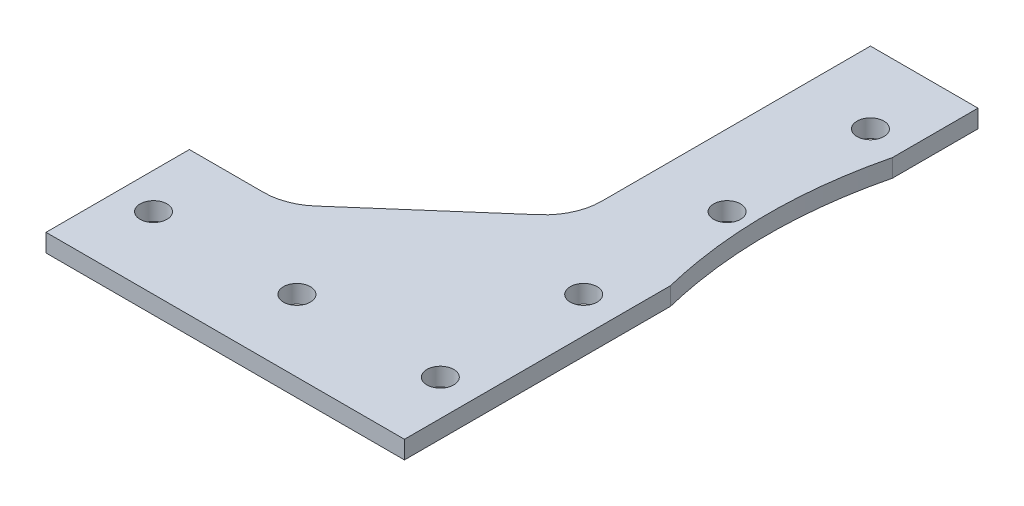
SolidWorks part; units mm, degrees
ref_plane "Front Plane" through (0, 0, 0) normal (0, 0, 1) x (1, 0, 0)
ref_plane "Top Plane" through (0, 0, 0) normal (0, 1, 0) x (1, 0, 0)
ref_plane "Right Plane" through (0, 0, 0) normal (1, 0, 0) x (0, 0, -1)
sketch "Sketch1" plane through (0, 0, 0) normal (0, 1, 0) x (1, 0, 0)
  line L1 (-31.75, 50.8) -> (31.75, 50.8)
  line L2 (-31.75, 50.8) -> (-31.75, -50.8)
  line L3 (-31.75, -50.8) -> (31.75, -50.8)
  line L4 (31.75, 50.8) -> (31.75, -50.8)
  line L5 (-31.75, 50.8) -> (31.75, -50.8) construction
  line L6 (-31.75, -50.8) -> (31.75, 50.8) construction
  point P0 (0, 0)
  dimension "D1" = 101.6
  dimension "D2" = 63.5
extrude "Boss-Extrude1" add sketch "Sketch1" along normal blind 3.175
sketch "Sketch2" plane through (0, 3.175, 0) normal (0, 1, 0) x (1, 0, 0)
  line L0 (-31.75, -50.8) -> (31.75, -50.8) construction
  line L1 (31.75, -50.8) -> (31.75, 50.8) construction
  circle A0 centre (25.4, -38.1) radius 2.3812
  circle A1 centre (25.4, -12.7) radius 2.3812
  circle A2 centre (25.4, 12.7) radius 2.3812
  circle A3 centre (25.4, 38.1) radius 2.3812
  circle A4 centre (0, -38.1) radius 2.3812
  circle A5 centre (-25.4, -38.1) radius 2.3812
  circle A6 centre (-50.8, -38.1) radius 2.3812
  dimension "D1" = 4.7625
  dimension "D2" = 12.7
  dimension "D3" = 6.35
  dimension "D4" = 4
  dimension "D5" = 4
extrude "Cut-Extrude1" cut sketch "Sketch2" against normal blind 3.175
sketch "Sketch3" plane through (0, 3.175, 0) normal (0, 1, 0) x (1, 0, 0)
  line L1 (-31.75, 50.8) -> (-31.75, -50.8) construction
  line L2 (31.75, 50.8) -> (-31.75, 50.8) construction
  line L3 (25.6187, 50.8) -> (-31.75, 50.8)
  line L4 (-31.75, 50.8) -> (-31.75, -36.9013)
  line L5 (-31.75, -25.4) -> (-14.7816, -25.4)
  line L6 (-14.7816, -25.4) -> (12.7, -1.3949)
  line L7 (12.7, -1.3949) -> (12.7, 50.8)
  line L8 (12.7, 50.8) -> (-32.5138, 50.8)
  line L9 (-32.5138, 50.8) -> (-31.75, -25.4)
  line L10 (31.75, -50.8) -> (31.75, 50.8) construction
  line L11 (-31.75, -50.8) -> (31.75, -50.8) construction
  line M12 (-31.75, 50.8) -> (-31.75, -50.8)
  dimension "D1" = 19.05
  dimension "D2" = 25.4
extrude "Cut-Extrude2" cut sketch "Sketch3" against normal through all contours L6 L7 L3 L5 M12 region at (-10.9345, 3.175, -15.9473)
fillet "Fillet1" radius 10.16 2 edges at (12.7, 1.5875, 1.3949) (-14.7816, 1.5875, 25.4)
sketch "Sketch4" plane through (0, 3.175, 0) normal (0, 1, 0) x (1, 0, 0)
  line L0 (31.75, -50.8) -> (31.75, 50.8) construction
  line L1 (31.75, 35.6528) -> (31.75, -3.6731)
  spline S0 degree 2 poles (31.75, 35.6528) (26.9513, 15.9884) (31.75, -3.6731) knots 0 0 0 1 1 1
extrude "Cut-Extrude3" cut sketch "Sketch4" against normal through all
